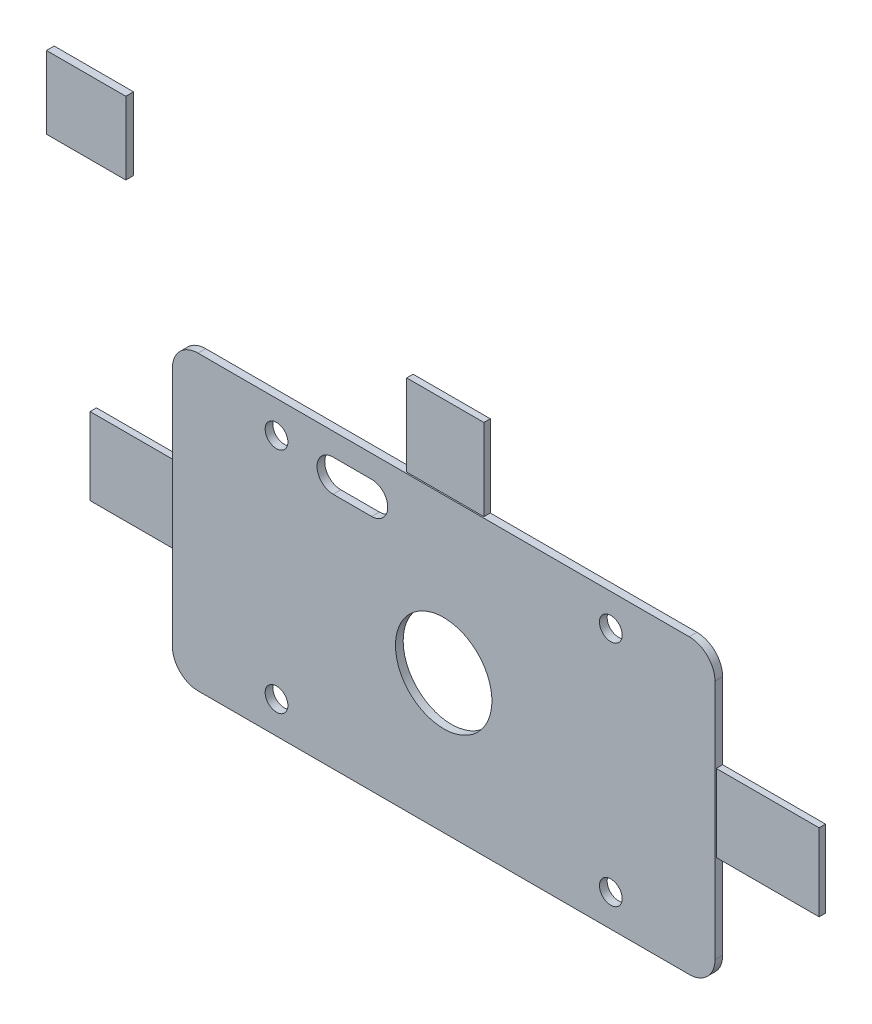
SolidWorks part; units mm, degrees
note: The reader was unsure of these and kept them because the rebuilt part matched: thickness of "Base-Flange1", "Sheet-Metal1", "Sheet-Metal2", "Sheet-Metal3", "Sheet-Metal4", "Sheet-Metal9".
material "5052-H32"
ref_plane "Front Plane" through (0, 0, 0) normal (0, 0, 1) x (1, 0, 0)
ref_plane "Top Plane" through (0, 0, 0) normal (0, 1, 0) x (1, 0, 0)
ref_plane "Right Plane" through (0, 0, 0) normal (1, 0, 0) x (0, 0, -1)
sketch "Sketch1" plane through (0, 0, 0) normal (0, 0, 1) x (1, 0, 0)
  line L1 (53.594, -28.8925) -> (-53.594, -28.8925)
  line L2 (53.594, -28.8925) -> (53.594, 28.8925)
  line L3 (53.594, 28.8925) -> (-53.594, 28.8925)
  line L4 (-53.594, -28.8925) -> (-53.594, 28.8925)
  line L5 (53.594, -28.8925) -> (-53.594, 28.8925) construction
  line L6 (53.594, 28.8925) -> (-53.594, -28.8925) construction
  point P0 (0, 0)
  dimension "D1" = 57.785
  dimension "D2" = 107.188
base flange "Base-Flange1" sketch "Sketch1" thickness 1.524 reverse thickness direction no parameters "D1"=0.7937
sketch "Sketch9" plane through (0, 0, -1.524) normal (0, 0, -1) x (-1, 0, 0)
  line L1 (0, -16.1925) -> (0, 13.0175) construction
  line L2 (53.594, -28.8925) -> (-53.594, -28.8925) construction
  line L5 (53.594, 28.8925) -> (53.594, -28.8925) construction
  line L6 (21.844, 18.0975) -> (21.844, 13.6525) construction
  line L7 (21.844, 24.4475) -> (21.844, 28.8925) construction
  line L8 (14.224, 24.4475) -> (21.844, 24.4475)
  line L9 (14.224, 18.0975) -> (21.844, 18.0975)
  line L10 (-53.594, 28.8925) -> (53.594, 28.8925) construction
  circle A0 centre (0, -1.5875) radius 9.525
  arc A1 (21.844, 18.0975) -> (21.844, 24.4475) centre (21.844, 21.2725) ccw
  arc A2 (14.224, 24.4475) -> (14.224, 18.0975) centre (14.224, 21.2725) ccw
  dimension "D1" = 19.05
  dimension "D2" = 4.445
  dimension "D4" = 6.35
  dimension "D3" = 15.875
  dimension "D7" = 7.62
  dimension "D8" = 31.75
  dimension "D9" = 12.7
hole_wizard "#16 (0.177) Diameter Hole1" positions "Sketch6" profile "Sketch7" hole size "#16" standard "ANSI Inch" end condition through all
sketch "Sketch6" plane through (0, 0, 0) normal (0, 0, 1) x (1, 0, 0)
  line L0 (-33.02, 28.8925) -> (-33.02, 22.5425) construction
  line L1 (53.594, 28.8925) -> (-53.594, 28.8925) construction
  line L2 (-33.02, 22.5425) -> (-53.594, 22.5425) construction
  line L3 (-53.594, 28.8925) -> (-53.594, -28.8925) construction
  line L5 (-33.02, -22.5425) -> (-53.594, -22.5425) construction
  line L6 (-53.594, -22.5425) -> (-33.02, -22.5425) construction
  line L7 (-33.02, -22.5425) -> (-33.02, -28.8925) construction
  line L8 (-53.594, -28.8925) -> (53.594, -28.8925) construction
  line L10 (33.02, -22.5425) -> (33.02, -28.8925) construction
  line L16 (33.02, 22.5425) -> (33.02, 28.8925) construction
  line L19 (33.02, -22.5425) -> (-33.02, -22.5425) construction
  line L21 (33.02, 22.5425) -> (-33.02, 22.5425) construction
  line L22 (33.02, 22.5425) -> (53.594, 22.5425) construction
  line L24 (53.594, -28.8925) -> (53.594, 28.8925) construction
  point P0 (-33.02, 22.5425)
  point P2 (33.02, 22.5425)
  point P4 (33.02, -22.5425)
  point P6 (-33.02, -22.5425)
  dimension "D1" = 6.35
  dimension "D2" = 66.04
sketch "Sketch7" plane through (-33.02, 22.5425, 0) normal (1, 0, 0) x (0, -1, 0)
  line L0 (0, 0) -> (0, 1.524)
  line L1 (0, 1.524) -> (2.2479, 1.524)
  line L2 (2.2479, 1.524) -> (2.2479, 0)
  line L5 (2.2479, 0) -> (0, 0)
  line L11 (0, -6.35) -> (0, 107.95) construction
  dimension "Thru Hole Dia." = 4.4958
  dimension "Thru Hole Depth" = 1.524
extrude "Cut-Extrude1" cut sketch "Sketch9" against normal through all normal cut yes
fillet "Fillet1" radius 5.08 4 edges at (-53.594, -28.8925, -0.762) (53.594, -28.8925, -0.762) (53.594, 28.8925, -0.762) (-53.594, 28.8925, -0.762)
sketch "Sketch10" plane through (0, 0, -1.524) normal (0, 0, -1) x (-1, 0, 0)
  line L0 (0, -1.5875) -> (-7.5513, 4.9682) construction
  line L1 (0, -1.5875) -> (9.4531, 1.6743) construction
  line L2 (0, -1.5875) -> (-1.9018, -11.405) construction
  circle A0 centre (0, -1.5875) radius 10 construction
  circle A1 centre (0, -1.5875) radius 30 construction
  dimension "D1" = 20
  dimension "D2" = 60
  dimension "D3" = 120
  dimension "D4" = 120
hole_wizard "Tap Drill for #4-40 Tap1" [suppressed] positions "Sketch12" profile "Sketch13" hole size "#4-40" standard "ANSI Inch"
sketch "Sketch12" plane through (0, 0, -1.524) normal (0, 0, -1) x (-1, 0, 0)
  line L1 (18.3186, 15.0551) -> (2.1894, 15.0551) construction
  line L3 (10.254, 15.0551) -> (10.254, 28.8925) construction
  line L5 (-48.514, 28.8925) -> (48.514, 28.8925) construction
  line L6 (53.594, 23.8125) -> (53.594, -23.8125) construction
  line L7 (10.254, 15.0551) -> (10.254, -28.8981) construction
  line L9 (18.3186, -28.8981) -> (2.1894, -28.8981) construction
  point P9 (2.1894, -28.8981)
  point P34 (2.1894, 15.0551)
  point P37 (4.0946, 20.7066)
  point P40 (18.3186, -28.8981)
  point P82 (10.254, -28.8981)
  dimension "D1" = 16.1293
  dimension "D2" = 13.8374
  dimension "D3" = 43.34
  dimension "D4" = 16.1293
  dimension "D5" = 43.9533
sketch "Sketch13" plane through (-2.1894, -28.8981, -1.524) normal (1, 0, 0) x (0, 1, 0)
  line L0 (0, 0) -> (0, 1.524)
  line L1 (0, 1.524) -> (1.1303, 1.524)
  line L2 (1.1303, 1.524) -> (1.1303, 0)
  line L5 (1.1303, 0) -> (0, 0)
  line L11 (0, -6.35) -> (0, 107.95) construction
  dimension "Thru Hole Dia." = 2.2606
  dimension "Thru Hole Depth" = 1.524
sketch "Sketch21" plane through (0, 0, -1.524) normal (0, 0, -1) x (-1, 0, 0)
  line L12 (62.7983, 65.7041) -> (78.4692, 65.7041)
  line L13 (62.7983, 65.7041) -> (62.7983, 51.3688)
  line L14 (62.7983, 51.3688) -> (78.4692, 51.3688)
  line L15 (78.4692, 65.7041) -> (78.4692, 51.3688)
  line L16 (62.7983, 65.7041) -> (78.4692, 51.3688) construction
  line L17 (62.7983, 51.3688) -> (78.4692, 65.7041) construction
  point P14 (70.6337, 58.5365)
extrude "Boss-Extrude2" add sketch "Sketch21" against normal up to surface (1.524 mm away) up to face at (-18.034, 21.2725, 0)
sketch "Sketch26" plane through (0, 0, -1.524) normal (0, 0, -1) x (-1, 0, 0)
  line L0 (53.594, 23.8125) -> (53.594, -23.8125) construction
  line L1 (53.594, 7.9797) -> (70.1146, 7.9797)
  line L2 (53.594, 7.9797) -> (53.594, -7.2603)
  line L3 (53.594, -7.2603) -> (70.1146, -7.2603)
  line L4 (70.1146, 7.9797) -> (70.1146, -7.2603)
  line L5 (53.594, 7.9797) -> (70.1146, -7.2603) construction
  line L6 (53.594, -7.2603) -> (70.1146, 7.9797) construction
  line L7 (-53.594, 8.7773) -> (-73.914, 8.7773)
  line L8 (-53.594, 8.7773) -> (-53.594, -6.4627)
  line L9 (-53.594, -6.4627) -> (-73.914, -6.4627)
  line L10 (-73.914, 8.7773) -> (-73.914, -6.4627)
  line L11 (-53.594, 8.7773) -> (-73.914, -6.4627) construction
  line L12 (-53.594, -6.4627) -> (-73.914, 8.7773) construction
  line L13 (7.5579, 28.8925) -> (-7.6821, 28.8925)
  line L14 (7.5579, 28.8925) -> (7.5579, 45.0124)
  line L15 (7.5579, 45.0124) -> (-7.6821, 45.0124)
  line L16 (-7.6821, 28.8925) -> (-7.6821, 45.0124)
  line L17 (7.5579, 28.8925) -> (-7.6821, 45.0124) construction
  line L18 (7.5579, 45.0124) -> (-7.6821, 28.8925) construction
  line L19 (-53.594, -23.8125) -> (-53.594, 23.8125) construction
  line L20 (-48.514, 28.8925) -> (48.514, 28.8925) construction
  point P4 (61.8543, 0.3597)
  point P9 (-63.754, 1.1573)
  point P14 (-0.0621, 36.9524)
  point P15 (70.1146, 0)
  point P16 (53.594, 7.9797)
  point P19 (-53.594, 9.9168)
  point P22 (-73.914, 8.7773)
  point P23 (-10.6736, 28.8925)
  point P26 (7.5579, 45.0124)
  dimension "D1" = 15.24
  dimension "D2" = 15.24
  dimension "D3" = 15.24
extrude "Boss-Extrude3" add sketch "Sketch26" against normal blind 1.27
sketch "Bend-Lines1" [suppressed] plane through (0, 0, 0) normal (0, 1, 0) x (1, 0, 0)
sketch "Bounding-Box1" [suppressed] plane through (0, 0, 0) normal (0, 1, 0) x (1, 0, 0)
sheet metal parameters "Sheet-Metal1" thickness 1.524 parameters "D1"=0.7937
flat pattern "Flat-Pattern1" [suppressed]
sketch "Bend-Lines2" plane through (0, 0, 0) normal (0, 1, 0) x (1, 0, 0)
sketch3d "Bounding-Box2" [suppressed]
  line L0 (41.275, 42.164, 0) -> (41.275, -42.164, 0) construction
  line L1 (-41.275, 42.164, 0) -> (-41.275, -42.164, 0) construction
  line L2 (41.275, 42.164, 0) -> (-41.275, 42.164, 0) construction
  line L3 (41.275, -42.164, 0) -> (-41.275, -42.164, 0) construction
sheet metal parameters "Sheet-Metal2" thickness 1.524 parameters "D1"=0.7937, "D7"=1.5875
flat pattern "Flat-Pattern1"
sketch "Bend-Lines2" plane through (0, 0, 0) normal (0, 1, 0) x (1, 0, 0)
sketch3d "Bounding-Box2" [suppressed]
  line L0 (41.275, 42.164, 0) -> (41.275, -42.164, 0) construction
  line L1 (-41.275, 42.164, 0) -> (-41.275, -42.164, 0) construction
  line L2 (41.275, 42.164, 0) -> (-41.275, 42.164, 0) construction
  line L3 (41.275, -42.164, 0) -> (-41.275, -42.164, 0) construction
sheet metal parameters "Sheet-Metal3" thickness 1.524 parameters "D1"=0.7937, "D7"=1.5875
flat pattern "Flat-Pattern1" [suppressed]
sketch "Bend-Lines2" plane through (0, 0, 0) normal (0, 1, 0) x (1, 0, 0)
sketch3d "Bounding-Box2" [suppressed]
  line L0 (-53.594, 28.8925, 0) -> (53.594, 28.8925, 0) construction
  line L1 (-53.594, -28.8925, 0) -> (53.594, -28.8925, 0) construction
  line L2 (-53.594, 28.8925, 0) -> (-53.594, -28.8925, 0) construction
  line L3 (53.594, 28.8925, 0) -> (53.594, -28.8925, 0) construction
sketch "Sketch10-1" plane through (0, 0, -1.524) normal (0, 0, -1) x (-1, 0, 0)
  line L0 (0, -1.5875) -> (-7.5513, 4.9682) construction
  line L1 (0, -1.5875) -> (9.4531, 1.6743) construction
  line L2 (0, -1.5875) -> (-1.9018, -11.405) construction
  circle A0 centre (0, -1.5875) radius 10 construction
  circle A1 centre (0, -1.5875) radius 30 construction
  dimension "D1" = 20
  dimension "D2" = 60
  dimension "D3" = 120
  dimension "D4" = 120
sketch "Sketch10-2" plane through (0, 0, -1.5875) normal (0, 0, -1) x (-1, 0, 0)
  circle A0 centre (-11.43, 6.35) radius 10
  dimension "D1" = 20
sketch "Sketch10-3" plane through (0, 0, -3.175) normal (0, 0, -1) x (-1, 0, 0)
  circle A0 centre (-11.43, 8.89) radius 10
  dimension "D1" = 20
sketch "Sketch10-7" plane through (0, 0, -1.5875) normal (0, 0, -1) x (-1, 0, 0)
  line L0 (-13.97, -1.27) -> (-11.3947, 8.3927) construction
  line L1 (-13.97, -1.27) -> (-6.8895, -8.3316) construction
  line L2 (-13.97, -1.27) -> (-23.6258, -3.8711) construction
  circle A0 centre (-13.97, -1.27) radius 10 construction
  circle A1 centre (-13.97, -1.27) radius 30 construction
  dimension "D1" = 20
  dimension "D2" = 60
  dimension "D3" = 120
  dimension "D4" = 120
sketch "Sketch10-20" plane through (0, 0, -1.524) normal (0, 0, -1) x (-1, 0, 0)
  line L0 (0, -1.5875) -> (-7.5513, 4.9682) construction
  line L1 (0, -1.5875) -> (9.4531, 1.6743) construction
  line L2 (0, -1.5875) -> (-1.9018, -11.405) construction
  circle A0 centre (0, -1.5875) radius 10 construction
  circle A1 centre (0, -1.5875) radius 30 construction
  dimension "D1" = 20
  dimension "D2" = 60
  dimension "D3" = 120
  dimension "D4" = 120
sheet metal parameters "Sheet-Metal4" thickness 1.524 parameters "D1"=0.7937, "D7"=1.5875
flat pattern "Flat-Pattern1" [suppressed]
sketch "Bend-Lines2" plane through (0, 0, 0) normal (0, 1, 0) x (1, 0, 0)
sketch3d "Bounding-Box2" [suppressed]
  line L0 (-53.594, -31.0515, 0) -> (53.594, -31.0515, 0) construction
  line L1 (-53.594, 31.0515, 0) -> (53.594, 31.0515, 0) construction
  line L2 (-53.594, -31.0515, 0) -> (-53.594, 31.0515, 0) construction
  line L3 (53.594, -31.0515, 0) -> (53.594, 31.0515, 0) construction
sketch "Sketch10-1" plane through (0, 0, -1.524) normal (0, 0, -1) x (-1, 0, 0)
  line L0 (0, -1.5875) -> (-7.5513, 4.9682) construction
  line L1 (0, -1.5875) -> (9.4531, 1.6743) construction
  line L2 (0, -1.5875) -> (-1.9018, -11.405) construction
  circle A0 centre (0, -1.5875) radius 10 construction
  circle A1 centre (0, -1.5875) radius 30 construction
  dimension "D1" = 20
  dimension "D2" = 60
  dimension "D3" = 120
  dimension "D4" = 120
sketch "Sketch10-2" plane through (0, 0, -1.5875) normal (0, 0, -1) x (-1, 0, 0)
  circle A0 centre (-11.43, 6.35) radius 10
  dimension "D1" = 20
sketch "Sketch10-3" plane through (0, 0, -3.175) normal (0, 0, -1) x (-1, 0, 0)
  circle A0 centre (-11.43, 8.89) radius 10
  dimension "D1" = 20
sketch "Sketch10-4" plane through (0, 0, -3.175) normal (0, 0, -1) x (-1, 0, 0)
  circle A0 centre (-11.43, 8.89) radius 10
  dimension "D1" = 20
sketch "Sketch10-5" plane through (0, 0, -3.175) normal (0, 0, -1) x (-1, 0, 0)
  line L0 (-11.43, 8.89) -> (-6.0662, 17.3297) construction
  line L1 (-11.43, 8.89) -> (-6.8029, 0.0249) construction
  line L2 (-11.43, 8.89) -> (-21.421, 9.3153) construction
  circle A0 centre (-11.43, 8.89) radius 10 construction
  circle A1 centre (-11.43, 8.89) radius 30 construction
  dimension "D1" = 20
  dimension "D2" = 60
  dimension "D3" = 120
  dimension "D4" = 120
sketch "Sketch10-6" plane through (0, 0, -3.175) normal (0, 0, -1) x (-1, 0, 0)
  line L0 (-13.97, -1.27) -> (-11.3947, 8.3927) construction
  line L1 (-13.97, -1.27) -> (-6.8895, -8.3316) construction
  line L2 (-13.97, -1.27) -> (-23.6258, -3.8711) construction
  circle A0 centre (-13.97, -1.27) radius 10 construction
  circle A1 centre (-13.97, -1.27) radius 30 construction
  dimension "D1" = 20
  dimension "D2" = 60
  dimension "D3" = 120
  dimension "D4" = 120
sketch "Sketch10-13" plane through (0, 0, -1.524) normal (0, 0, -1) x (-1, 0, 0)
  line L0 (-13.97, -1.27) -> (-11.3947, 8.3927) construction
  line L1 (-13.97, -1.27) -> (-6.8895, -8.3316) construction
  line L2 (-13.97, -1.27) -> (-23.6258, -3.8711) construction
  circle A0 centre (-13.97, -1.27) radius 10 construction
  circle A1 centre (-13.97, -1.27) radius 30 construction
  dimension "D1" = 20
  dimension "D2" = 60
  dimension "D3" = 120
  dimension "D4" = 120
sketch "Sketch10-14" plane through (0, 0, -1.524) normal (0, 0, -1) x (-1, 0, 0)
  line L0 (-13.97, -1.27) -> (-11.3947, 8.3927) construction
  line L1 (-13.97, -1.27) -> (-6.8895, -8.3316) construction
  line L2 (-13.97, -1.27) -> (-23.6258, -3.8711) construction
  circle A0 centre (-13.97, -1.27) radius 10 construction
  circle A1 centre (-13.97, -1.27) radius 30 construction
  dimension "D1" = 20
  dimension "D2" = 60
  dimension "D3" = 120
  dimension "D4" = 120
sketch "Sketch10-17" plane through (0, 0, -1.524) normal (0, 0, -1) x (-1, 0, 0)
  line L0 (-13.97, -1.27) -> (-11.3947, 8.3927) construction
  line L1 (-13.97, -1.27) -> (-6.8895, -8.3316) construction
  line L2 (-13.97, -1.27) -> (-23.6258, -3.8711) construction
  circle A0 centre (-13.97, -1.27) radius 10 construction
  circle A1 centre (-13.97, -1.27) radius 30 construction
  dimension "D1" = 20
  dimension "D2" = 60
  dimension "D3" = 120
  dimension "D4" = 120
sketch "Sketch10-18" plane through (0, 0, -1.524) normal (0, 0, -1) x (-1, 0, 0)
  line L0 (-13.97, -4.7625) -> (-12.0489, 5.0512) construction
  line L1 (-13.97, -4.7625) -> (-6.4316, -11.3331) construction
  line L2 (-13.97, -4.7625) -> (-23.4295, -8.0056) construction
  circle A0 centre (-13.97, -4.7625) radius 10 construction
  circle A1 centre (-13.97, -4.7625) radius 30 construction
  dimension "D1" = 20
  dimension "D2" = 60
  dimension "D3" = 120
  dimension "D4" = 120
sketch "Sketch10-19" plane through (0, 0, -1.524) normal (0, 0, -1) x (-1, 0, 0)
  line L0 (0.254, -1.5875) -> (-7.4054, 4.8416) construction
  line L1 (0.254, -1.5875) -> (9.6515, 1.8312) construction
  line L2 (0.254, -1.5875) -> (-1.484, -11.4353) construction
  circle A0 centre (0.254, -1.5875) radius 10 construction
  circle A1 centre (0.254, -1.5875) radius 30 construction
  dimension "D1" = 20
  dimension "D2" = 60
  dimension "D3" = 120
  dimension "D4" = 120
sheet metal parameters "Sheet-Metal7" thickness 1.5875 parameters "D1"=0.7937
flat pattern "Flat-Pattern7" [suppressed]
sketch "Bend-Lines4" plane through (0, 0, 0) normal (0, 1, 0) x (1, 0, 0)
sketch3d "Bounding-Box4" [suppressed]
  line L0 (-52.759, -34.544, 0) -> (53.5019, -34.544, 0) construction
  line L1 (-52.759, 47.8767, 0) -> (53.5019, 47.8767, 0) construction
  line L2 (-52.759, -34.544, 0) -> (-52.759, 47.8767, 0) construction
  line L3 (53.5019, -34.544, 0) -> (53.5019, 47.8767, 0) construction
sketch "Sketch10-9" plane through (0, 0, -1.524) normal (0, 0, -1) x (-1, 0, 0)
  line L0 (-13.97, -1.27) -> (-11.3947, 8.3927) construction
  line L1 (-13.97, -1.27) -> (-6.8895, -8.3316) construction
  line L2 (-13.97, -1.27) -> (-23.6258, -3.8711) construction
  circle A0 centre (-13.97, -1.27) radius 10 construction
  circle A1 centre (-13.97, -1.27) radius 30 construction
  dimension "D1" = 20
  dimension "D2" = 60
  dimension "D3" = 120
  dimension "D4" = 120
sketch "Sketch10-10" plane through (0, 0, -1.524) normal (0, 0, -1) x (-1, 0, 0)
  line L0 (-13.97, -1.27) -> (-11.3947, 8.3927) construction
  line L1 (-13.97, -1.27) -> (-6.8895, -8.3316) construction
  line L2 (-13.97, -1.27) -> (-23.6258, -3.8711) construction
  circle A0 centre (-13.97, -1.27) radius 10 construction
  circle A1 centre (-13.97, -1.27) radius 30 construction
  dimension "D1" = 20
  dimension "D2" = 60
  dimension "D3" = 120
  dimension "D4" = 120
sheet metal parameters "Sheet-Metal9" thickness 1.524 parameters "D1"=0.7937, "D7"=1.5875
flat pattern "Flat-Pattern1" [suppressed]
sketch "Bend-Lines2" plane through (0, 0, 0) normal (0, 1, 0) x (1, 0, 0)
sketch3d "Bounding-Box2" [suppressed]
  line L0 (-53.594, 28.8925, 0) -> (53.594, 28.8925, 0) construction
  line L1 (-53.594, -28.8925, 0) -> (53.594, -28.8925, 0) construction
  line L2 (-53.594, 28.8925, 0) -> (-53.594, -28.8925, 0) construction
  line L3 (53.594, 28.8925, 0) -> (53.594, -28.8925, 0) construction
sketch "Sketch10-1" plane through (0, 0, -1.524) normal (0, 0, -1) x (-1, 0, 0)
  line L0 (0, -1.5875) -> (-7.5513, 4.9682) construction
  line L1 (0, -1.5875) -> (9.4531, 1.6743) construction
  line L2 (0, -1.5875) -> (-1.9018, -11.405) construction
  circle A0 centre (0, -1.5875) radius 10 construction
  circle A1 centre (0, -1.5875) radius 30 construction
  dimension "D1" = 20
  dimension "D2" = 60
  dimension "D3" = 120
  dimension "D4" = 120
sketch "Sketch10-2" plane through (0, 0, -1.5875) normal (0, 0, -1) x (-1, 0, 0)
  circle A0 centre (-11.43, 6.35) radius 10
  dimension "D1" = 20
sketch "Sketch10-3" plane through (0, 0, -3.175) normal (0, 0, -1) x (-1, 0, 0)
  circle A0 centre (-11.43, 8.89) radius 10
  dimension "D1" = 20
sketch "Sketch10-4" plane through (0, 0, -3.175) normal (0, 0, -1) x (-1, 0, 0)
  circle A0 centre (-11.43, 8.89) radius 10
  dimension "D1" = 20
sketch "Sketch10-5" plane through (0, 0, -3.175) normal (0, 0, -1) x (-1, 0, 0)
  line L0 (-11.43, 8.89) -> (-6.0662, 17.3297) construction
  line L1 (-11.43, 8.89) -> (-6.8029, 0.0249) construction
  line L2 (-11.43, 8.89) -> (-21.421, 9.3153) construction
  circle A0 centre (-11.43, 8.89) radius 10 construction
  circle A1 centre (-11.43, 8.89) radius 30 construction
  dimension "D1" = 20
  dimension "D2" = 60
  dimension "D3" = 120
  dimension "D4" = 120
sketch "Sketch10-6" plane through (0, 0, -3.175) normal (0, 0, -1) x (-1, 0, 0)
  line L0 (-13.97, -1.27) -> (-11.3947, 8.3927) construction
  line L1 (-13.97, -1.27) -> (-6.8895, -8.3316) construction
  line L2 (-13.97, -1.27) -> (-23.6258, -3.8711) construction
  circle A0 centre (-13.97, -1.27) radius 10 construction
  circle A1 centre (-13.97, -1.27) radius 30 construction
  dimension "D1" = 20
  dimension "D2" = 60
  dimension "D3" = 120
  dimension "D4" = 120
sketch "Sketch10-11" plane through (0, 0, -1.524) normal (0, 0, -1) x (-1, 0, 0)
  line L0 (-13.97, -1.27) -> (-11.3947, 8.3927) construction
  line L1 (-13.97, -1.27) -> (-6.8895, -8.3316) construction
  line L2 (-13.97, -1.27) -> (-23.6258, -3.8711) construction
  circle A0 centre (-13.97, -1.27) radius 10 construction
  circle A1 centre (-13.97, -1.27) radius 30 construction
  dimension "D1" = 20
  dimension "D2" = 60
  dimension "D3" = 120
  dimension "D4" = 120
sketch "Sketch10-12" plane through (0, 0, -1.524) normal (0, 0, -1) x (-1, 0, 0)
  line L0 (-13.97, -1.27) -> (-11.3947, 8.3927) construction
  line L1 (-13.97, -1.27) -> (-6.8895, -8.3316) construction
  line L2 (-13.97, -1.27) -> (-23.6258, -3.8711) construction
  circle A0 centre (-13.97, -1.27) radius 10 construction
  circle A1 centre (-13.97, -1.27) radius 30 construction
  dimension "D1" = 20
  dimension "D2" = 60
  dimension "D3" = 120
  dimension "D4" = 120
sketch "Sketch10-15" plane through (0, 0, -1.524) normal (0, 0, -1) x (-1, 0, 0)
  line L0 (-13.97, -1.27) -> (-11.3947, 8.3927) construction
  line L1 (-13.97, -1.27) -> (-6.8895, -8.3316) construction
  line L2 (-13.97, -1.27) -> (-23.6258, -3.8711) construction
  circle A0 centre (-13.97, -1.27) radius 10 construction
  circle A1 centre (-13.97, -1.27) radius 30 construction
  dimension "D1" = 20
  dimension "D2" = 60
  dimension "D3" = 120
  dimension "D4" = 120
sketch "Sketch10-16" plane through (0, 0, -1.524) normal (0, 0, -1) x (-1, 0, 0)
  line L0 (-13.97, -1.27) -> (-11.3947, 8.3927) construction
  line L1 (-13.97, -1.27) -> (-6.8895, -8.3316) construction
  line L2 (-13.97, -1.27) -> (-23.6258, -3.8711) construction
  circle A0 centre (-13.97, -1.27) radius 10 construction
  circle A1 centre (-13.97, -1.27) radius 30 construction
  dimension "D1" = 20
  dimension "D2" = 60
  dimension "D3" = 120
  dimension "D4" = 120
sketch "Sketch10-22" plane through (0, 0, -1.524) normal (0, 0, -1) x (-1, 0, 0)
  line L0 (0, -1.5875) -> (-7.5513, 4.9682) construction
  line L1 (0, -1.5875) -> (9.4531, 1.6743) construction
  line L2 (0, -1.5875) -> (-1.9018, -11.405) construction
  circle A0 centre (0, -1.5875) radius 10 construction
  circle A1 centre (0, -1.5875) radius 30 construction
  dimension "D1" = 20
  dimension "D2" = 60
  dimension "D3" = 120
  dimension "D4" = 120
sheet metal parameters "Sheet-Metal10" thickness 1.5875 parameters "D1"=0.7937
flat pattern "Flat-Pattern10" [suppressed]
sketch "Bend-Lines5" plane through (0, 0, 0) normal (0, 1, 0) x (1, 0, 0)
sketch3d "Bounding-Box5" [suppressed]
  line L0 (-53.594, 28.8925, 0) -> (53.594, 28.8925, 0) construction
  line L1 (-53.594, -28.8925, 0) -> (53.594, -28.8925, 0) construction
  line L2 (-53.594, 28.8925, 0) -> (-53.594, -28.8925, 0) construction
  line L3 (53.594, 28.8925, 0) -> (53.594, -28.8925, 0) construction
sketch "Sketch10-21" plane through (0, 0, -1.524) normal (0, 0, -1) x (-1, 0, 0)
  line L0 (0, -1.5875) -> (-7.5513, 4.9682) construction
  line L1 (0, -1.5875) -> (9.4531, 1.6743) construction
  line L2 (0, -1.5875) -> (-1.9018, -11.405) construction
  circle A0 centre (0, -1.5875) radius 10 construction
  circle A1 centre (0, -1.5875) radius 30 construction
  dimension "D1" = 20
  dimension "D2" = 60
  dimension "D3" = 120
  dimension "D4" = 120
